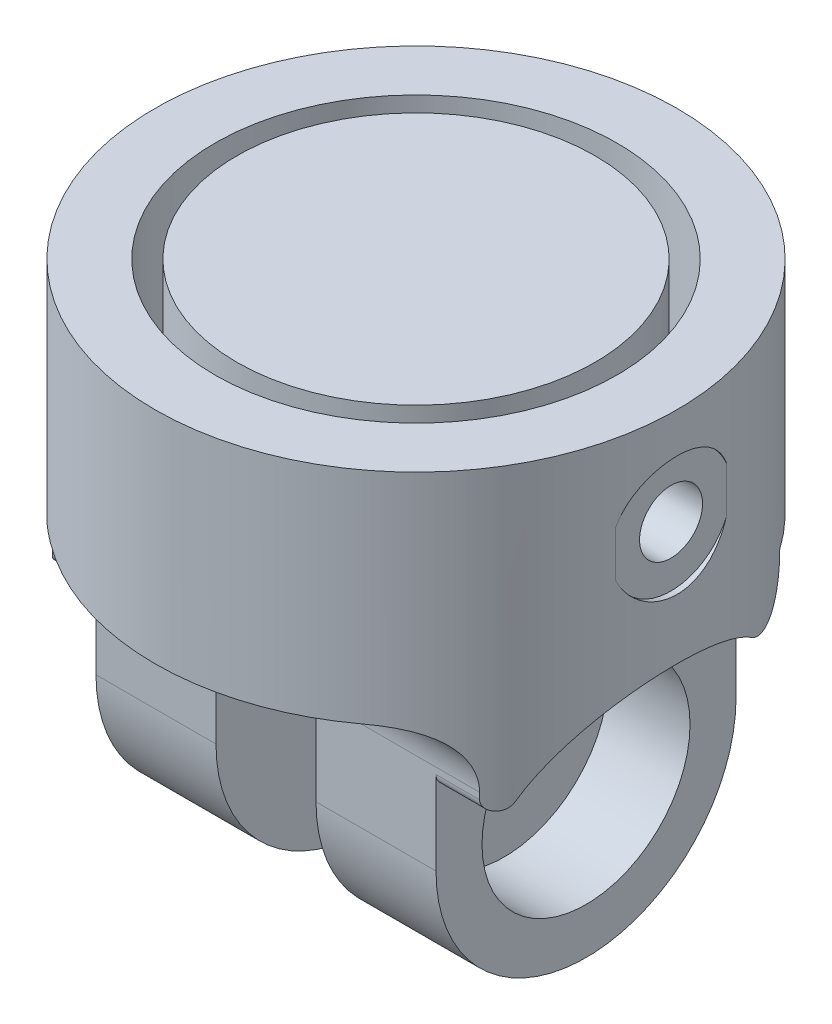
SolidWorks part; units mm, degrees
material "PLA Black"
ref_plane "Front" through (0, 0, 0) normal (0, 0, 1) x (1, 0, 0)
ref_plane "Top" through (0, 0, 0) normal (0, 1, 0) x (1, 0, 0)
ref_plane "Right" through (0, 0, 0) normal (1, 0, 0) x (0, 0, -1)
sketch "Sketch1" plane through (0, 0, 0) normal (0, 1, 0) x (1, 0, 0)
  line L0 (0, 8.95) -> (0, 10.05) construction
  circle A0 centre (0, 0) radius 10.05
  circle A1 centre (0, 0) radius 13.05
  circle A2 centre (0, 0) radius 9.5 construction
  circle A4 centre (0, 0) radius 8.95
  point P11 (0, 9.5)
  dimension "D1" = 1.1
  dimension "D2" = 3
  dimension "D3" = 19
extrude "Boss-Extrude1" add sketch "Sketch1" along normal blind 10 contours A1 A0 | A4 region at (-12.6809, 0, 0) region at (0, 0, 0)
sketch "Sketch3" plane through (0, 0, 0) normal (0, -1, 0) x (1, 0, 0)
  circle A2 centre (0, 0) radius 13.05 construction
  circle A3 centre (0, 0) radius 13.05
extrude "Boss-Extrude2" add sketch "Sketch3" along normal blind 1
sketch "Sketch4" plane through (0, -1, 0) normal (0, -1, 0) x (1, 0, 0)
  line L0 (0, 17.8908) -> (0, -17.0763) construction
  line L1 (2.5, 7.5) -> (8.5, 7.5)
  line L2 (2.5, 7.5) -> (2.5, -7.5)
  line L3 (2.5, -7.5) -> (8.5, -7.5)
  line L4 (8.5, 7.5) -> (8.5, -7.5)
  line L5 (-8.5, 7.5) -> (-8.5, -7.5)
  line L6 (-2.5, -7.5) -> (-8.5, -7.5)
  line L7 (-2.5, 7.5) -> (-2.5, -7.5)
  line L8 (-2.5, 7.5) -> (-8.5, 7.5)
  line L9 (16.8049, 0) -> (-19.8998, 0) construction
  dimension "D1" = 6
  dimension "D2" = 5
  dimension "D3" = 15
extrude "Boss-Extrude3" add sketch "Sketch4" along normal blind 15
sketch "Sketch5" plane through (8.5, 0, 0) normal (1, 0, 0) x (0, 0, -1)
  line L0 (-7.5, -16) -> (-7.5, -1) construction
  line L1 (7.5, -16) -> (7.5, -1) construction
  line L2 (7.5, -8.5) -> (7.5, -17.1619)
  line L3 (7.5, -17.1619) -> (-7.5, -17.1619)
  line L4 (-7.5, -17.1619) -> (-7.5, -8.5)
  arc A0 (-7.5, -8.5) -> (7.5, -8.5) centre (0, -8.5) ccw
  circle A1 centre (0, -8.5) radius 1.55
  dimension "D1" = 3.1
extrude "Cut-Extrude1" cut sketch "Sketch5" against normal through all both and the other way through all
sketch "Sketch6" plane through (8.5, 0, 0) normal (1, 0, 0) x (0, 0, -1)
  circle A0 centre (0, -8.5) radius 5.2
  dimension "D1" = 10.4
extrude "Cut-Extrude2" cut sketch "Sketch6" against normal blind 4.1
mirror "Mirror1" about plane through (0, 0, 0) normal (1, 0, 0) of "Cut-Extrude2"
ref_plane "Plane9" through (1.65, 0, 0) normal (1, 0, 0) x (0, 0, -1)
sketch "Sketch7" plane through (1.65, 0, 0) normal (1, 0, 0) x (0, 0, -1)
  line L0 (3.4, -8.5) -> (3.4, -1) construction
  line L1 (7.5, -1) -> (-7.5, -1) construction
  line L2 (3.3065, -7.7081) -> (1.7, -1) construction
  line L3 (3.0306, -6.9587) -> (0, -1) construction
  line L4 (1.7, -0.6757) -> (1.7, -1.4422) construction
  line L5 (2.6419, -6.3598) -> (-1.7, -1) construction
  line L6 (2.2408, -5.9429) -> (-3.4, -1) construction
  line L8 (0, -1.6788) -> (0, 0) construction
  line L9 (-8.4824, -8.5) -> (8.712, -8.5) construction
  line L10 (1.8898, -5.6736) -> (-5.1, -1) construction
  line L11 (-3.4, -0.3587) -> (-3.4, -1.6788) construction
  circle A0 centre (0, -8.5) radius 3.4 construction
  dimension "D1" = 6.8
  dimension "D2" = 33.768
  dimension "D3" = 7.5
ref_plane "Plane1" through (1.65, -1, -3.4) normal (0, 1, 0) x (1, 0, 0)
ref_plane "Plane2" through (1.65, -1, -1.7) normal (0, 0.9725, 0.2329) x (1, 0, 0)
ref_plane "Plane3" through (1.65, -1, 0) normal (0, 0.8913, 0.4533) x (1, 0, 0)
ref_plane "Plane5" through (1.65, -1, 1.7) normal (0, 0.777, 0.6295) x (1, 0, 0)
ref_plane "Plane6" through (1.65, -1, 3.4) normal (0, 0.659, 0.7521) x (1, 0, 0)
ref_plane "Plane7" through (1.65, -1, 5.1) normal (0, 0.5558, 0.8313) x (1, 0, 0)
sketch "Sketch8" plane through (1.65, -1, -3.4) normal (0, 1, 0) x (1, 0, 0)
  circle A0 centre (0, 0) radius 0.605
  dimension "D1" = 1.21
extrude "Cut-Extrude5" cut sketch "Sketch8" along normal blind 5.5 and the other way through all
sketch "Sketch9" plane through (1.65, -1, -1.7) normal (0, 0.9725, 0.2329) x (1, 0, 0)
  circle A0 centre (0, 0) radius 0.605
  dimension "D1" = 1.21
extrude "Cut-Extrude3" cut sketch "Sketch9" along normal blind 5.5
sketch "Sketch10" plane through (1.65, -1, 0) normal (0, 0.8913, 0.4533) x (1, 0, 0)
  circle A0 centre (0, 0) radius 0.605
  dimension "D1" = 1.21
sketch "Sketch11" plane through (1.65, -1, 1.7) normal (0, 0.777, 0.6295) x (1, 0, 0)
  circle A0 centre (0, 0) radius 0.605
  dimension "D1" = 1.21
sketch "Sketch12" plane through (1.65, -1, 3.4) normal (0, 0.659, 0.7521) x (1, 0, 0)
  circle A0 centre (0, 0) radius 0.605
  dimension "D1" = 1.21
sketch "Sketch14" plane through (1.65, -1, 5.1) normal (0, 0.5558, 0.8313) x (1, 0, 0)
  circle A0 centre (0, 0) radius 0.605
  dimension "D1" = 1.21
extrude "Cut-Extrude6" cut sketch "Sketch10" along normal blind 5.5 and the other way through all
extrude "Cut-Extrude7" cut sketch "Sketch11" along normal blind 5.5 and the other way through all contours A0
extrude "Cut-Extrude8" cut sketch "Sketch12" along normal blind 5.5 and the other way through all contours A0
extrude "Cut-Extrude9" cut sketch "Sketch14" along normal blind 5.5 and the other way through all contours A0
ref_plane "Plane8" through (13.05, 0, 0) normal (1, 0, 0) x (0, 0, -1)
hole_wizard "Tap Drill for M3 Helicoil1" positions "Sketch17" profile "Sketch18" hole size "M3x0.5" standard "DIN"
sketch "Sketch17" plane through (13.05, 0, 0) normal (1, 0, 0) x (0, 0, -1)
  line L0 (-22.2973, 5) -> (18.0703, 5) construction
  line L4 (0, 12.2732) -> (0, -5.3405) construction
  line L6 (-7.5, -8.5) -> (-7.5, -1) construction
  line L7 (7.5, -8.5) -> (7.5, -1) construction
  line L8 (13.05, 10) -> (-13.05, 10) construction
  line L9 (10.05, 0) -> (-10.05, 0) construction
  point P0 (0, 5)
sketch "Sketch18" plane through (13.05, 5, 0) normal (0, 1, 0) x (0, 0, -1)
  line L0 (0, 0) -> (0, 6.9464)
  line L1 (0, 6.9464) -> (1.575, 6)
  line L2 (1.575, 6) -> (1.575, 0)
  line L5 (1.575, 0) -> (0, 0)
  line L10 (0, 6.9464) -> (-1.575, 6) construction
  line L11 (0, -6.35) -> (0, 107.95) construction
  dimension "Hole Dia." = 3.15
  dimension "Hole Depth" = 6
  dimension "Drill Angle" = 118
sketch "Sketch20" plane through (13.05, 0, 0) normal (1, 0, 0) x (0, 0, -1)
  circle A0 centre (0, 5) radius 3
  dimension "D1" = 6
extrude "Cut-Extrude10" cut sketch "Sketch20" against normal blind 0.3
sketch "Sketch21" plane through (8.5, 0, 0) normal (1, 0, 0) x (0, 0, -1)
  line L0 (7.5, -1) -> (-7.5, -1) construction
  line L1 (7.5, -0.1252) -> (7.5, -1.1767)
  line L2 (0.9244, -19.0662) -> (-4.8209, -14.2453) construction
  line L3 (0, 5.2718) -> (0, -9.2894) construction
  line L4 (0, 10) -> (0, -1) construction
  line L5 (-7.5, -0.1252) -> (-7.5, -4.3226)
  line L6 (7.5, -0.1252) -> (-7.5, -0.1252)
  line L7 (-7.5, -8.5) -> (-7.5, -1) construction
  line L8 (7.5, -8.5) -> (7.5, -1) construction
  line L9 (0, -1) -> (9.4693, -4.4465) construction
  line L10 (0, -1) -> (1.6171, -0.0664) construction
  line L11 (4.6128, -2.5863) -> (7.5, -1.1767) construction
  line L12 (10.5662, -7.5756) -> (4.8209, -2.7547) construction
  line L13 (-4.8209, -14.2453) -> (4.8209, -2.7547) construction
  line L14 (10.5662, -7.5756) -> (0.9244, -19.0662) construction
  arc A0 (-6.4204, -4.6233) -> (4.6128, -2.5863) centre (0, -8.5) cw
  arc A1 (-6.4204, -4.6233) -> (-7.5, -4.3226) centre (-6.9183, -4.3226) cw
  arc A2 (7.5, -1.1767) -> (4.6128, -2.5863) centre (5.7123, -1.1767) cw
  circle A3 centre (0, -8.5) radius 1.55 construction
  arc A4 (-4.8209, -14.2453) -> (4.8209, -2.7547) centre (0, -8.5) cw construction
  dimension "D1" = 30
  dimension "D3" = 7.5
  dimension "D2" = 50
  dimension "D4" = 15
extrude "Boss-Extrude4" add sketch "Sketch21" along normal up to surface (2.1795 mm away) up to face at (12.895, 5, 0)
mirror "Mirror2" about plane through (0, 0, 0) normal (1, 0, 0) of "Boss-Extrude4", "Tap Drill for M3 Helicoil1", "Cut-Extrude10"
fillet "Fillet1" radius 3 2 edges at (-6.5898, -1, 7.5) (6.5898, -1, 7.5)
equation "\"knee_angle\"= 70"
equation "\"ankle_angle\" = 80"
equation "\"hip_angle\" = 40"
equation "\"spring_ankle_parallel_arm_diameter\"= 1.1"
equation "\"spring_ankle_parallel_arm_length\"= 13"
equation "\"spring_ankle_parallel_intern_diameter\"= 5.7"
equation "\"spring_ankle_parallel_angle\"= \"ankle_angle\""
equation "\"spring_ankle_parallel_turns\"= 3"
equation "\"spring_ankle_parallel_pitch\"= \"spring_ankle_parallel_arm_diameter\" * 1.01"
equation "\"spring_ankle_parallel_cutting_distance\"= (1-\"spring_ankle_parallel_angle\" / 360) * \"spring_ankle_parallel_pitch\""
equation "\"spring_ankle_serial_arm_diameter\"= 1.91"
equation "\"spring_ankle_serial_arm_length\"= 10"
equation "\"spring_ankle_serial_intern_diameter\"= 5.7"
equation "\"spring_ankle_serial_angle\"= \"90\""
equation "\"spring_ankle_serial_turns\"= 3"
equation "\"spring_ankle_serial_pitch\"= \"spring_ankle_serial_arm_diameter\" * 1.01"
equation "\"spring_ankle_serial_cutting_distance\"= (1-\"spring_ankle_serial_angle\" / 360) * \"spring_ankle_serial_pitch\""
equation "\"spring_knee_parallel_arm_diameter\"= 1.1"
equation "\"spring_knee_parallel_arm_length\"= 13"
equation "\"spring_knee_parallel_intern_diameter\"= 5.7"
equation "\"spring_knee_parallel_angle\"= -\"knee_angle\" + 90"
equation "\"spring_knee_parallel_turns\"= 3"
equation "\"spring_knee_parallel_pitch\"= \"spring_knee_parallel_arm_diameter\" * 1.01"
equation "\"spring_knee_parallel_cutting_distance\"= (1-(\"spring_knee_parallel_angle\") / 360) * \"spring_knee_parallel_pitch\""
equation "\"spring_knee_serial_arm_diameter\"= 1.91"
equation "\"spring_knee_serial_arm_length\"= 10"
equation "\"spring_knee_serial_intern_diameter\"= 5.7"
equation "\"spring_knee_serial_angle\"= \"90\""
equation "\"spring_knee_serial_turns\"= 3"
equation "\"spring_knee_serial_pitch\"= \"spring_knee_serial_arm_diameter\" * 1.01"
equation "\"spring_knee_serial_cutting_distance\"= (1-\"spring_knee_serial_angle\" / 360) * \"spring_knee_serial_pitch\""
equation "\"spring_ankle_parallel_nominal_diameter\"= \"spring_ankle_parallel_arm_diameter\" + \"spring_ankle_parallel_intern_diameter\""
equation "\"spring_ankle_serial_nominal_diameter\"= \"spring_ankle_serial_arm_diameter\" + \"spring_ankle_serial_intern_diameter\""
equation "\"spring_knee_parallel_nominal_diameter\"= \"spring_knee_parallel_arm_diameter\" + \"spring_knee_parallel_intern_diameter\""
equation "\"spring_knee_serial_nominal_diameter\"= \"spring_knee_serial_arm_diameter\" + \"spring_knee_serial_intern_diameter\""
equation "\"D1@Sketch7\"=\"spring_ankle_parallel_nominal_diameter\""
equation "\"D1@Sketch8\"=\"spring_ankle_parallel_arm_diameter\"*1.1"
equation "\"D1@Sketch9\"=\"spring_ankle_parallel_arm_diameter\"*1.1"
equation "\"D1@Sketch10\"=\"spring_ankle_parallel_arm_diameter\"*1.1"
equation "\"D1@Sketch11\"=\"spring_ankle_parallel_arm_diameter\"*1.1"
equation "\"D1@Sketch12\"=\"spring_ankle_parallel_arm_diameter\"*1.1"
equation "\"D1@Sketch14\"=\"spring_ankle_parallel_arm_diameter\"*1.1"
equation "\"D1@Cut-Extrude3\"=\"spring_ankle_parallel_arm_length\"-\"axis_structure_distance\""
equation "\"axis_structure_distance\"= 7.5"
equation "\"D1@Cut-Extrude5\"=\"spring_ankle_parallel_arm_length\"-\"axis_structure_distance\""
equation "\"D1@Cut-Extrude6\"=\"spring_ankle_parallel_arm_length\"-\"axis_structure_distance\""
equation "\"D1@Cut-Extrude7\"=\"spring_ankle_parallel_arm_length\"-\"axis_structure_distance\""
equation "\"D1@Cut-Extrude8\"=\"spring_ankle_parallel_arm_length\"-\"axis_structure_distance\""
equation "\"D1@Cut-Extrude9\"=\"spring_ankle_parallel_arm_length\"-\"axis_structure_distance\""
equation "\"D1@Boss-Extrude3\"=\"axis_structure_distance\"*2"
equation "\"ankle_angle_max\" = 120"
equation "\"ankle_angle_min\" = 50"
equation "\"knee_angle_max\" = 120"
equation "\"knee_angle_min\" = 0"
equation "\"hip_angle_max\" = 90"
equation "\"hip_angle_min\" = -60"
equation "\"D1@Sketch21\"=\"ankle_angle_max\"-90"
equation "\"D2@Sketch21\"=\"ankle_angle_min\""
equation "\"D1@Plane9\"=(\"spring_ankle_parallel_arm_diameter\"*\"spring_ankle_parallel_turns\")/2"
